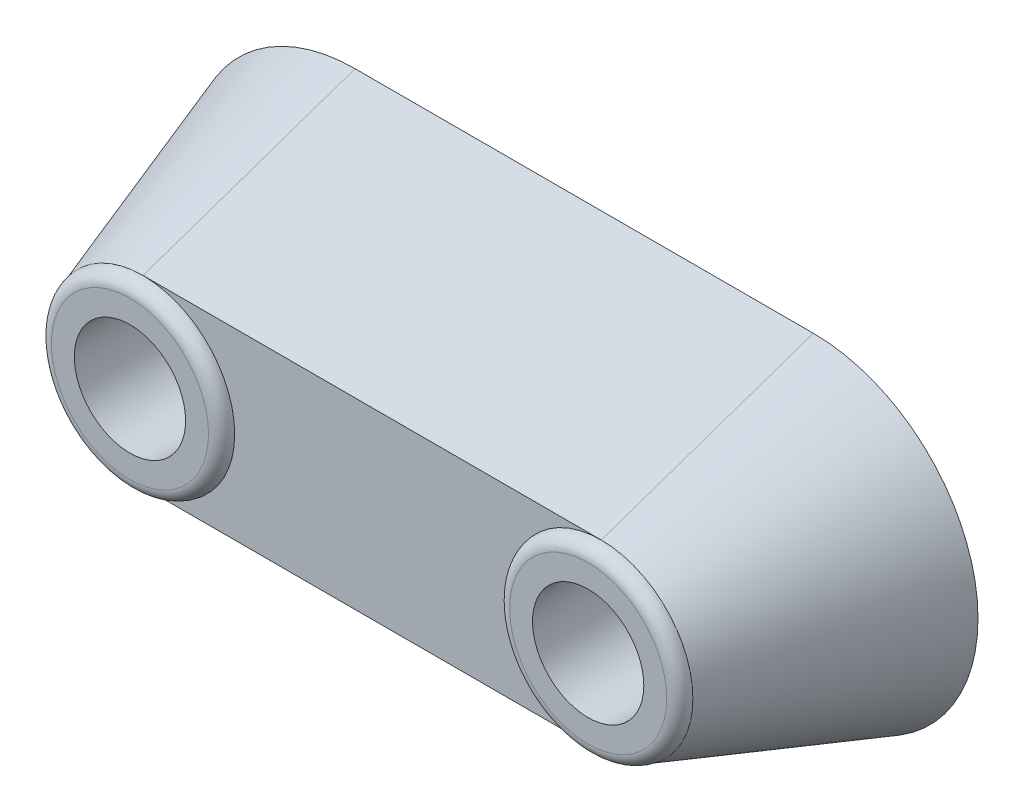
SolidWorks part; units mm, degrees
material "ABS"
ref_plane "Front Plane" through (0, 0, 0) normal (0, 0, 1) x (1, 0, 0)
ref_plane "Top Plane" through (0, 0, 0) normal (0, 1, 0) x (1, 0, 0)
ref_plane "Right Plane" through (0, 0, 0) normal (1, 0, 0) x (0, 0, -1)
sketch "Sketch1" plane through (0, 0, 0) normal (0, 0, 1) x (1, 0, 0)
  line L0 (0, 26) -> (0, 33.5) construction
  line L1 (9, -33.5) -> (-26, -33.5)
  line L3 (10, 33.5) -> (-10, 33.5)
  line L4 (-15, -14.5) -> (-15, 28.5)
  line L5 (14.0406, -31.3572) -> (-15, 33.5) construction
  line L6 (15, 33.5) -> (-15, -33.5) construction
  line L7 (-10, 28.5) -> (10, 28.5)
  line L8 (-10, 28.5) -> (-10, 23.5)
  line L9 (-10, 23.5) -> (10, 23.5)
  line L10 (10, 28.5) -> (10, 23.5)
  line L11 (-10, 28.5) -> (10, 23.5) construction
  line L12 (-10, 23.5) -> (10, 28.5) construction
  line L13 (9, -26.5) -> (-26, -26.5) construction
  line L14 (-26, -19.5) -> (-20, -19.5)
  line L15 (15, -22.8944) -> (15, 28.5)
  line L16 (-15, -19.5) -> (-15, -33.5) construction
  line L17 (15, -22.8944) -> (15, -33.5) construction
  line L18 (14.0406, -31.3572) -> (15, -33.5) construction
  circle A0 centre (9, -26.5) radius 4.25
  circle A1 centre (-26, -26.5) radius 4.25
  arc A2 (-26, -19.5) -> (-26, -33.5) centre (-26, -26.5) ccw
  arc A3 (9, -33.5) -> (15, -22.8944) centre (9, -26.5) ccw
  arc A4 (-20, -19.5) -> (-15, -14.5) centre (-20, -14.5) ccw
  arc A5 (15, 28.5) -> (10, 33.5) centre (10, 28.5) ccw
  arc A6 (-10, 33.5) -> (-15, 28.5) centre (-10, 28.5) ccw
  point P0 (0, 0)
  point P5 (0, 26)
  dimension "D6" = 8.5
  dimension "D7" = 35
  dimension "D8" = 7
  dimension "D9" = 6
  dimension "D10" = 8.5
  dimension "D11" = 14
  dimension "D12" = 5
  dimension "D1" = 30
  dimension "D2" = 33.5
  dimension "D3" = 20
  dimension "D4" = 5
  dimension "D5" = 5
extrude "Boss-Extrude1" add sketch "Sketch1" along normal blind 3
sketch "Sketch2" plane through (0, 0, 3) normal (0, 0, 1) x (1, 0, 0)
  circle A0 centre (-26, -26.5) radius 7
  circle A1 centre (9, -26.5) radius 7
  circle A2 centre (-26, -26.5) radius 4.25
  circle A3 centre (9, -26.5) radius 4.25
  circle A4 centre (-26, -26.5) radius 4.25 construction
  circle A5 centre (9, -26.5) radius 4.25 construction
  arc A6 (-26, -19.5) -> (-26, -33.5) centre (-26, -26.5) ccw construction
  arc A7 (9, -33.5) -> (15, -22.8944) centre (9, -26.5) ccw construction
extrude "Boss-Extrude2" add sketch "Sketch2" along normal blind 1
fillet "Fillet1" radius 1 2 edges at (16, -26.5, 4) (-19, -26.5, 4)
sketch "Sketch3" plane through (0, 0, 3) normal (0, 0, 1) x (1, 0, 0)
  line L0 (10, 33.5) -> (-10, 33.5) construction
  line L1 (-20, -19.5) -> (9, -19.5)
  line L2 (-20, -19.5) -> (-20, 33.5)
  line L3 (-20, 33.5) -> (15, 33.5)
  line L4 (15, -22.8944) -> (15, 33.5)
  line L5 (15, -22.8944) -> (15, 28.5) construction
  arc A0 (-20, -19.5) -> (-15, -14.5) centre (-20, -14.5) ccw construction
  arc A1 (15, -22.8944) -> (9, -19.5) centre (9, -26.5) ccw
extrude "Cut-Extrude1" cut sketch "Sketch3" against normal through all
sketch "Sketch4" plane through (0, 0, 3) normal (0, 0, 1) x (1, 0, 0)
  line L0 (-26, -26.5) -> (9, -26.5) construction
  line L1 (-26, -19.5) -> (9, -19.5)
  line L2 (-26, -33.5) -> (9, -33.5)
  arc A0 (-26, -19.5) -> (-26, -33.5) centre (-26, -26.5) ccw
  arc A1 (9, -33.5) -> (9, -19.5) centre (9, -26.5) ccw
  arc A2 (9, -33.5) -> (9, -19.5) centre (9, -26.5) ccw construction
  point P4 (-8.5, -26.5)
extrude "Boss-Extrude3" add sketch "Sketch4" against normal blind 16.2 draft 19 draft outward yes
sketch "Sketch5" plane through (0, 0, 3) normal (0, 0, 1) x (1, 0, 0)
  circle A0 centre (-26, -26.5) radius 4.25
  circle A1 centre (9, -26.5) radius 4.25
  circle A2 centre (9, -26.5) radius 4.25 construction
  circle A3 centre (-26, -26.5) radius 4.25 construction
extrude "Cut-Extrude2" cut sketch "Sketch5" against normal through all
